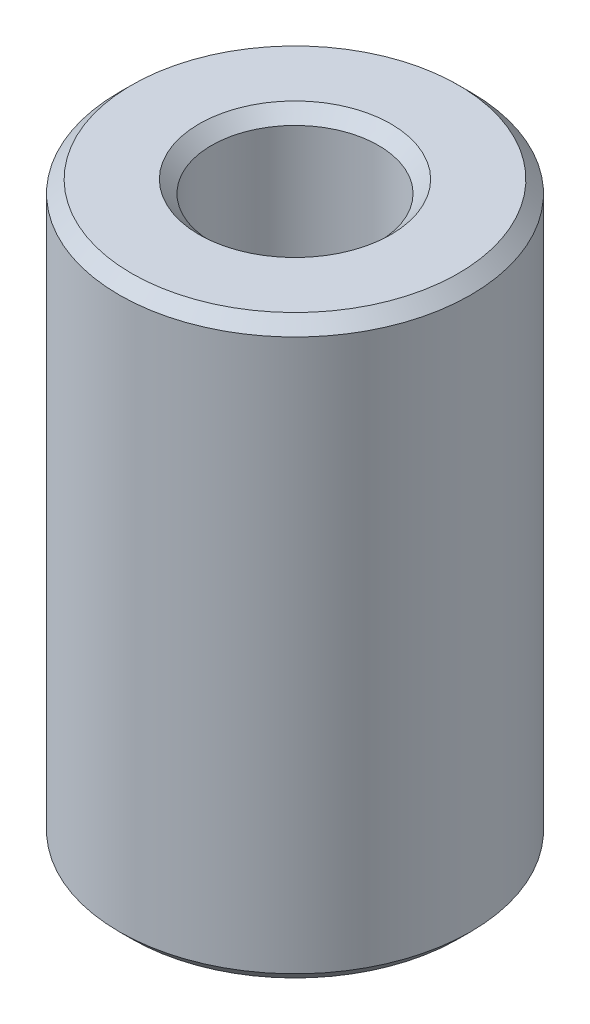
SolidWorks part; units mm, degrees
ref_plane "Front Plane" through (0, 0, 0) normal (0, 0, 1) x (1, 0, 0)
ref_plane "Top Plane" through (0, 0, 0) normal (0, 1, 0) x (1, 0, 0)
ref_plane "Right Plane" through (0, 0, 0) normal (1, 0, 0) x (0, 0, -1)
sketch "Sketch1" plane through (0, 0, 0) normal (0, 1, 0) x (1, 0, 0)
  circle A0 centre (0, 0) radius 55
  dimension "SLEEVE_OD" = 110
extrude "Boss-Extrude1" add sketch "Sketch1" along normal blind 180.4097
sketch "Sketch2" plane through (0, 0, 0) normal (0, 1, 0) x (1, 0, 0)
  circle A0 centre (0, 0) radius 26.1426
  dimension "BORE_D" = 52.2852
extrude "Cut-Extrude1" cut sketch "Sketch2" along normal through all
chamfer "Chamfer1" distance 3.8886 angle 45 4 edges at (0, 180.4097, 26.1426) (0, 0, 26.1426) (0, 0, 55) (0, 180.4097, 55)
